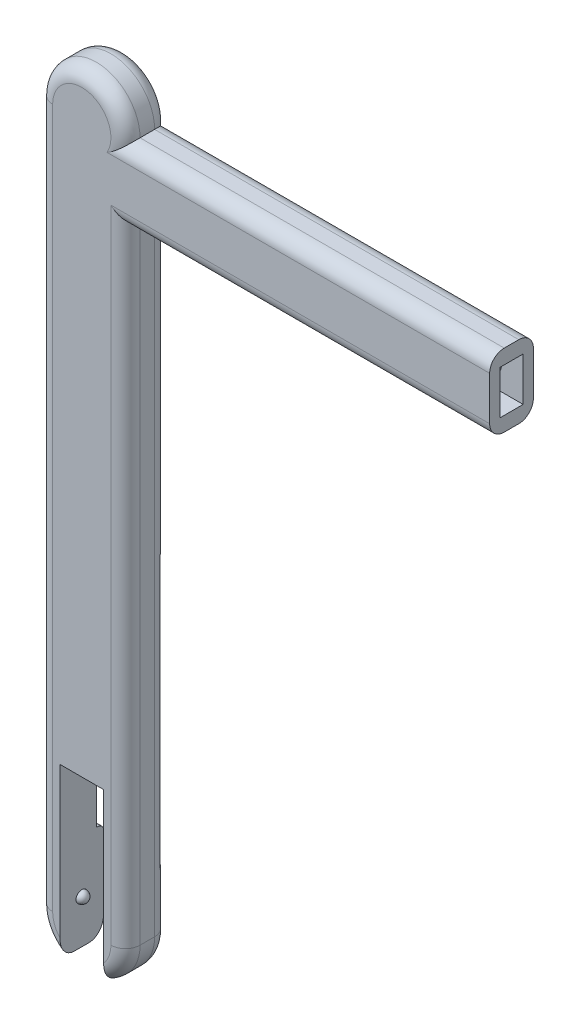
SolidWorks part; units mm, degrees
ref_plane "Front Plane" through (0, 0, 0) normal (0, 0, 1) x (1, 0, 0)
ref_plane "Top Plane" through (0, 0, 0) normal (0, 1, 0) x (1, 0, 0)
ref_plane "Right Plane" through (0, 0, 0) normal (1, 0, 0) x (0, 0, -1)
sketch "Sketch1" plane through (0, 0, 0) normal (0, 0, 1) x (1, 0, 0)
  line L0 (0, -103.2558) -> (0, 136.7442) construction
  line L1 (-15, -103.2558) -> (-15, 136.7442)
  line L2 (15, -103.2558) -> (15, 111.7442)
  line L3 (15, 136.7442) -> (140, 136.7442)
  line L4 (140, 136.7442) -> (140, 111.7442)
  line L5 (140, 111.7442) -> (15, 111.7442)
  arc A0 (-15, -103.2558) -> (15, -103.2558) centre (0, -103.2558) ccw
  arc A1 (15, 136.7442) -> (-15, 136.7442) centre (0, 136.7442) ccw
  point P3 (0, 16.7442)
  dimension "D2" = 15
  dimension "D1" = 240
  dimension "D3" = 125
  dimension "D4" = 25
extrude "Boss-Extrude1" add sketch "Sketch1" along normal blind 15
fillet "Fillet1" radius 5 12 edges at (0, 151.7442, 0) (-15, 16.7442, 0) (0, -118.2558, 0) (0, 151.7442, 15) (15, 4.2442, 15) (0, -118.2558, 15) (15, 4.2442, 0) (77.5, 136.7442, 15) (77.5, 136.7442, 0) (77.5, 111.7442, 0) (77.5, 111.7442, 15) (-15, 16.7442, 15)
sketch "Sketch2" plane through (140, 0, 0) normal (1, 0, 0) x (0, 0, -1)
  line L0 (-10, 111.7442) -> (-5, 111.7442) construction
  line L1 (-11.5, 131.7442) -> (-3.5, 131.7442)
  line L2 (-11.5, 131.7442) -> (-11.5, 116.7442)
  line L3 (-11.5, 116.7442) -> (-3.5, 116.7442)
  line L4 (-3.5, 131.7442) -> (-3.5, 116.7442)
  line L6 (-15, 116.7442) -> (-15, 131.7442) construction
  dimension "D1" = 8
  dimension "D2" = 15
  dimension "D3" = 5
  dimension "D4" = 3.5
extrude "Cut-Extrude1" cut sketch "Sketch2" against normal blind 100
sketch "Sketch3" plane through (0, 0, 15) normal (0, 0, 1) x (1, 0, 0)
  line L0 (-10, 136.7442) -> (-10, -103.2558) construction
  line L1 (-7.5, -118.2558) -> (7.5, -118.2558)
  line L2 (-7.5, -118.2558) -> (-7.5, -58.2558)
  line L3 (-7.5, -58.2558) -> (7.5, -58.2558)
  line L4 (7.5, -118.2558) -> (7.5, -58.2558)
  arc A0 (-15, -103.2558) -> (15, -103.2558) centre (0, -103.2558) ccw construction
  dimension "D1" = 15
  dimension "D2" = 60
  dimension "D3" = 2.5
extrude "Cut-Extrude3" cut sketch "Sketch3" against normal blind 100
ref_plane "Plane1" through (0, 0, 7.5) normal (0, 0, 1) x (1, 0, 0)
sketch "Sketch6" plane through (0, 0, 7.5) normal (0, 0, 1) x (1, 0, 0)
  line L0 (22.7951, -101.2558) -> (-27.1938, -101.2558) construction
  line L1 (7.5, -58.2558) -> (-7.5, -58.2558) construction
  line L2 (-7.5, -101.2558) -> (-5.5, -101.2558)
  line L3 (-7.5, -58.2558) -> (-7.5, -109.8702) construction
  line L4 (-7.5, -99.2558) -> (-7.5, -101.2558)
  line L5 (0, 28.4206) -> (0, -140.8487) construction
  line L6 (7.5, -101.2558) -> (5.5, -101.2558)
  line L7 (7.5, -109.8702) -> (7.5, -58.2558) construction
  line L8 (7.5, -99.2558) -> (7.5, -101.2558)
  arc A0 (-5.5, -101.2558) -> (-7.5, -99.2558) centre (-7.5, -101.2558) ccw
  arc A1 (5.5, -101.2558) -> (7.5, -99.2558) centre (7.5, -101.2558) cw
  dimension "D1" = 43
  dimension "D2" = 2
  dimension "D3" = 2
revolve "Revolve1" add sketch "Sketch6" angle 360 about L0
sketch "Sketch8" plane through (0, 0, 0) normal (1, 0, 0) x (0, 0, -1)
  line L1 (-7.5, 85.25) -> (-7.5, -85.25) construction
  line L2 (0, -103.2558) -> (0, 136.7442) construction
  line L6 (-7.5, 91.7442) -> (0, 86.4926)
  line L9 (-7.5, 81.7442) -> (-7.5, 91.7442)
  line L25 (0, 56.4926) -> (0, 66.4926)
  line L26 (-7.5, 71.7442) -> (0, 66.4926)
  line L27 (-7.5, 81.7442) -> (0, 76.4926)
  line L28 (0, 76.4926) -> (0, 86.4926)
  line L29 (-7.5, 61.7442) -> (-7.5, 71.7442)
  line L30 (-7.5, 61.7442) -> (0, 56.4926)
  line L31 (0, 36.4926) -> (0, 46.4926)
  line L32 (-7.5, 51.7442) -> (0, 46.4926)
  line L33 (-7.5, 41.7442) -> (-7.5, 51.7442)
  line L34 (-7.5, 41.7442) -> (0, 36.4926)
  dimension "D5" = 55
  dimension "D6" = 10
  dimension "D7" = 3
extrude "Cut-Extrude4" cut sketch "Sketch8" against normal mid plane 7.5
sketch "Sketch9" plane through (0, 0, 0) normal (0, 0, -1) x (-1, 0, 0)
  line L0 (-15, 111.7442) -> (-140, 111.7442) construction
  line L1 (-140, 116.7442) -> (-140, 131.7442) construction
  circle A0 centre (-130, 124.2442) radius 2.5
  circle A1 centre (-110, 124.2442) radius 2.5
  circle A2 centre (-90, 124.2442) radius 2.5
  circle A3 centre (-70, 124.2442) radius 2.5
  circle A4 centre (-50, 124.2442) radius 2.5
  dimension "D2" = 5
  dimension "D1" = 12.5
  dimension "D4" = 10
  dimension "D3" = 5
extrude "Cut-Extrude5" cut sketch "Sketch9" against normal blind 7.5
sketch "Sketch10" plane through (-15, 0, 0) normal (-1, 0, 0) x (0, 0, 1)
  line L0 (0, -83.2558) -> (2.5, -83.2558)
  line L1 (0, -103.2558) -> (0, 136.7442) construction
  line L2 (2.5, -83.2558) -> (2.5, 6.7442)
  line L3 (2.5, 6.7442) -> (0, 6.7442)
  line L4 (0, 6.7442) -> (0, -83.2558)
  dimension "D1" = 90
  dimension "D2" = 20
  dimension "D3" = 2.5
extrude "Cut-Extrude6" cut sketch "Sketch10" against normal through all
fillet "Fillet2" radius 2 7 edges at (12.5, 6.7442, 0.6699) (-12.5, 6.7442, 0.6699) (-12.5, -83.2558, 0.6699) (12.5, -83.2558, 0.6699) (0, 6.7442, 0) (-8.75, -83.2558, 0) (8.75, -83.2558, 0)
sketch "Sketch11" plane through (-15, 0, 0) normal (-1, 0, 0) x (0, 0, 1)
  line L0 (0, 109.2442) -> (0, 101.2442)
  line L1 (0, 8.7442) -> (0, 136.7442) construction
  line L4 (-3, 104.2442) -> (-7, 104.2442)
  line L5 (-7, 104.2442) -> (-7, 109.2442)
  line L6 (-7, 109.2442) -> (0, 109.2442)
  arc A0 (0, 101.2442) -> (-3, 104.2442) centre (-3, 101.2442) ccw
  dimension "D1" = 3
  dimension "D2" = 5
  dimension "D3" = 7
  dimension "D4" = 15.5
extrude "Boss-Extrude2" add sketch "Sketch11" against normal blind 19
sketch "Sketch12" plane through (0, 0, -7) normal (0, 0, -1) x (-1, 0, 0)
  line L0 (3.75, 100.7129) -> (3.75, 111.6456)
  line L1 (3.75, 111.6456) -> (16.7615, 111.6456)
  line L2 (16.7615, 111.6456) -> (16.7615, 100.7129)
  line L3 (16.7615, 100.7129) -> (3.75, 100.7129)
  line L4 (3.75, 91.7442) -> (3.75, 81.7442) construction
extrude "Cut-Extrude7" cut sketch "Sketch12" against normal blind 7
